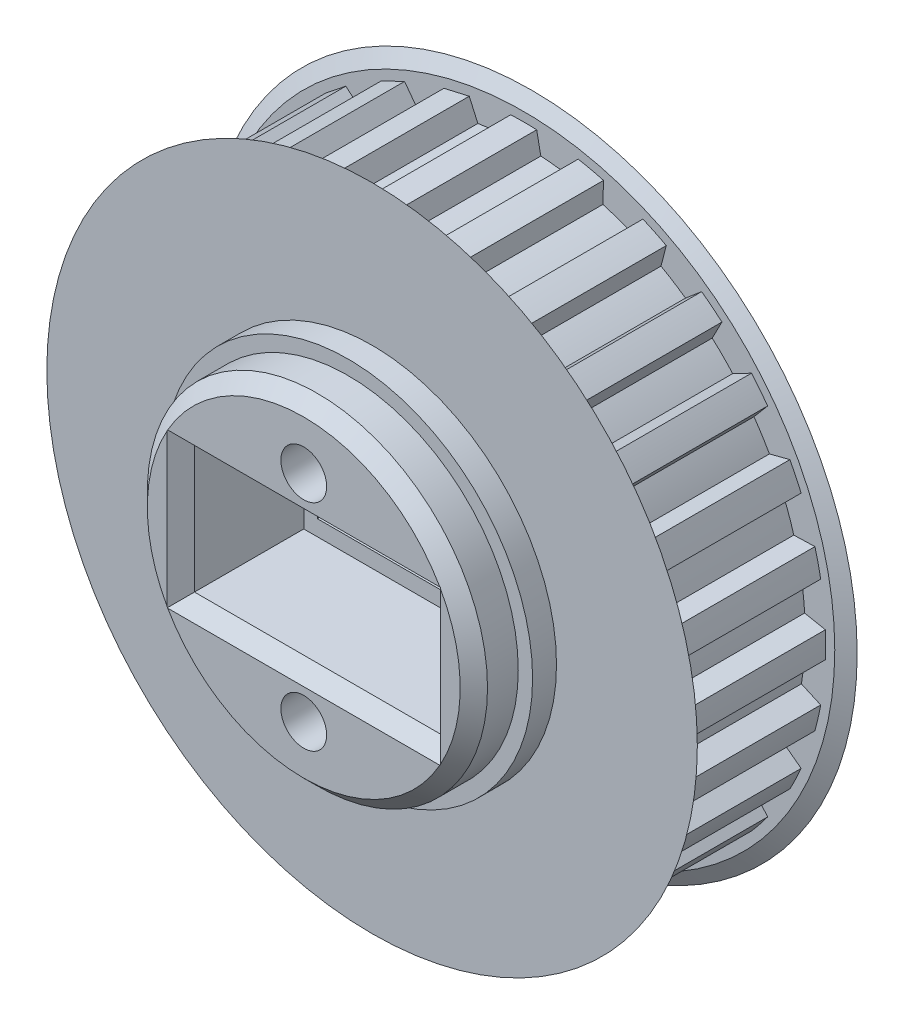
SolidWorks part; units mm, degrees
material "ABS"
ref_plane "Alzado" through (0, 0, 0) normal (0, 0, 1) x (1, 0, 0)
ref_plane "Planta" through (0, 0, 0) normal (0, 1, 0) x (1, 0, 0)
ref_plane "Vista lateral" through (0, 0, 0) normal (1, 0, 0) x (0, 0, -1)
sketch "Croquis1" plane through (0, 0, 0) normal (0, 0, 1) x (1, 0, 0)
  line L0 (0, 0) -> (0, 14.5885) construction
  line L1 (-0.95, 22.0796) -> (-1.25, 20.562)
  line L2 (0.95, 22.0796) -> (1.25, 20.562)
  line L3 (5.8393, 21.3146) -> (5.7941, 19.7684)
  line L4 (3.987, 21.7374) -> (3.3568, 20.3247)
  line L5 (10.4359, 19.4808) -> (10.0477, 17.9834)
  line L6 (8.724, 20.3052) -> (7.7953, 19.0681)
  line L7 (14.5091, 16.6702) -> (13.7975, 15.2967)
  line L8 (13.0236, 17.8548) -> (11.8429, 16.8554)
  line L9 (17.8548, 13.0236) -> (16.8554, 11.8429)
  line L10 (16.6702, 14.5091) -> (15.2967, 13.7975)
  line L11 (20.3052, 8.724) -> (19.0681, 7.7953)
  line L12 (19.4808, 10.4359) -> (17.9834, 10.0477)
  line L13 (21.7374, 3.987) -> (20.3247, 3.3568)
  line L14 (21.3146, 5.8393) -> (19.7684, 5.7941)
  line L15 (22.0796, -0.95) -> (20.562, -1.25)
  line L16 (22.0796, 0.95) -> (20.562, 1.25)
  line L17 (21.3146, -5.8393) -> (19.7684, -5.7941)
  line L18 (21.7374, -3.987) -> (20.3247, -3.3568)
  line L19 (19.4808, -10.4359) -> (17.9834, -10.0477)
  line L20 (20.3052, -8.724) -> (19.0681, -7.7953)
  line L21 (16.6702, -14.5091) -> (15.2967, -13.7975)
  line L22 (17.8548, -13.0236) -> (16.8554, -11.8429)
  line L23 (13.0236, -17.8548) -> (11.8429, -16.8554)
  line L24 (14.5091, -16.6702) -> (13.7975, -15.2967)
  line L25 (8.724, -20.3052) -> (7.7953, -19.0681)
  line L26 (10.4359, -19.4808) -> (10.0477, -17.9834)
  line L27 (3.987, -21.7374) -> (3.3568, -20.3247)
  line L28 (5.8393, -21.3146) -> (5.7941, -19.7684)
  line L29 (-0.95, -22.0796) -> (-1.25, -20.562)
  line L30 (0.95, -22.0796) -> (1.25, -20.562)
  line L31 (-5.8393, -21.3146) -> (-5.7941, -19.7684)
  line L32 (-3.987, -21.7374) -> (-3.3568, -20.3247)
  line L33 (-10.4359, -19.4808) -> (-10.0477, -17.9834)
  line L34 (-8.724, -20.3052) -> (-7.7953, -19.0681)
  line L35 (-14.5091, -16.6702) -> (-13.7975, -15.2967)
  line L36 (-13.0236, -17.8548) -> (-11.8429, -16.8554)
  line L37 (-17.8548, -13.0236) -> (-16.8554, -11.8429)
  line L38 (-16.6702, -14.5091) -> (-15.2967, -13.7975)
  line L39 (-20.3052, -8.724) -> (-19.0681, -7.7953)
  line L40 (-19.4808, -10.4359) -> (-17.9834, -10.0477)
  line L41 (-21.7374, -3.987) -> (-20.3247, -3.3568)
  line L42 (-21.3146, -5.8393) -> (-19.7684, -5.7941)
  line L43 (-22.0796, 0.95) -> (-20.562, 1.25)
  line L44 (-22.0796, -0.95) -> (-20.562, -1.25)
  line L45 (-21.3146, 5.8393) -> (-19.7684, 5.7941)
  line L46 (-21.7374, 3.987) -> (-20.3247, 3.3568)
  line L47 (-19.4808, 10.4359) -> (-17.9834, 10.0477)
  line L48 (-20.3052, 8.724) -> (-19.0681, 7.7953)
  line L49 (-16.6702, 14.5091) -> (-15.2967, 13.7975)
  line L50 (-17.8548, 13.0236) -> (-16.8554, 11.8429)
  line L51 (-13.0236, 17.8548) -> (-11.8429, 16.8554)
  line L52 (-14.5091, 16.6702) -> (-13.7975, 15.2967)
  line L53 (-14.5091, 16.6702) -> (-13.0236, 17.8548)
  line L54 (-8.724, 20.3052) -> (-7.7953, 19.0681)
  line L55 (-10.4359, 19.4808) -> (-10.0477, 17.9834)
  line L56 (-10.4359, 19.4808) -> (-8.724, 20.3052)
  line L57 (-3.987, 21.7374) -> (-3.3568, 20.3247)
  line L58 (-5.8393, 21.3146) -> (-5.7941, 19.7684)
  line L59 (-5.8393, 21.3146) -> (-3.987, 21.7374)
  arc A0 (-13.7975, 15.2967) -> (-15.2967, 13.7975) centre (0, 0) ccw
  arc A1 (3.3568, 20.3247) -> (1.25, 20.562) centre (0, 0) ccw
  arc A2 (-10.0477, 17.9834) -> (-11.8429, 16.8554) centre (0, 0) ccw
  arc A3 (-5.7941, 19.7684) -> (-7.7953, 19.0681) centre (0, 0) ccw
  arc A9 (-16.6702, 14.5091) -> (-17.8548, 13.0236) centre (0, 0) ccw
  arc A10 (-19.4808, 10.4359) -> (-20.3052, 8.724) centre (0, 0) ccw
  arc A11 (5.8393, 21.3146) -> (3.987, 21.7374) centre (0, 0) ccw
  arc A12 (0.95, 22.0796) -> (-0.95, 22.0796) centre (0, 0) ccw
  arc A16 (10.4359, 19.4808) -> (8.724, 20.3052) centre (0, 0) ccw
  arc A17 (14.5091, 16.6702) -> (13.0236, 17.8548) centre (0, 0) ccw
  arc A18 (17.8548, 13.0236) -> (16.6702, 14.5091) centre (0, 0) ccw
  arc A19 (20.3052, 8.724) -> (19.4808, 10.4359) centre (0, 0) ccw
  arc A20 (21.7374, 3.987) -> (21.3146, 5.8393) centre (0, 0) ccw
  arc A21 (22.0796, -0.95) -> (22.0796, 0.95) centre (0, 0) ccw
  arc A22 (21.3146, -5.8393) -> (21.7374, -3.987) centre (0, 0) ccw
  arc A23 (19.4808, -10.4359) -> (20.3052, -8.724) centre (0, 0) ccw
  arc A24 (16.6702, -14.5091) -> (17.8548, -13.0236) centre (0, 0) ccw
  arc A25 (13.0236, -17.8548) -> (14.5091, -16.6702) centre (0, 0) ccw
  arc A26 (-5.8393, -21.3146) -> (-3.987, -21.7374) centre (0, 0) ccw
  arc A27 (-10.4359, -19.4808) -> (-8.724, -20.3052) centre (0, 0) ccw
  arc A28 (-14.5091, -16.6702) -> (-13.0236, -17.8548) centre (0, 0) ccw
  arc A29 (-20.3052, -8.724) -> (-19.4808, -10.4359) centre (0, 0) ccw
  arc A30 (-21.7374, -3.987) -> (-21.3146, -5.8393) centre (0, 0) ccw
  arc A31 (-22.0796, 0.95) -> (-22.0796, -0.95) centre (0, 0) ccw
  arc A32 (-21.3146, 5.8393) -> (-21.7374, 3.987) centre (0, 0) ccw
  arc A33 (-0.95, -22.0796) -> (0.95, -22.0796) centre (0, 0) ccw
  arc A34 (3.987, -21.7374) -> (5.8393, -21.3146) centre (0, 0) ccw
  arc A35 (8.724, -20.3052) -> (10.4359, -19.4808) centre (0, 0) ccw
  arc A36 (7.7953, 19.0681) -> (5.7941, 19.7684) centre (0, 0) ccw
  arc A37 (11.8429, 16.8554) -> (10.0477, 17.9834) centre (0, 0) ccw
  arc A39 (-1.25, 20.562) -> (-3.3568, 20.3247) centre (0, 0) ccw
  arc A43 (15.2967, 13.7975) -> (13.7975, 15.2967) centre (0, 0) ccw
  arc A44 (17.9834, 10.0477) -> (16.8554, 11.8429) centre (0, 0) ccw
  arc A45 (19.7684, 5.7941) -> (19.0681, 7.7953) centre (0, 0) ccw
  arc A46 (20.562, 1.25) -> (20.3247, 3.3568) centre (0, 0) ccw
  arc A47 (20.3247, -3.3568) -> (20.562, -1.25) centre (0, 0) ccw
  arc A48 (19.0681, -7.7953) -> (19.7684, -5.7941) centre (0, 0) ccw
  arc A49 (16.8554, -11.8429) -> (17.9834, -10.0477) centre (0, 0) ccw
  arc A50 (13.7975, -15.2967) -> (15.2967, -13.7975) centre (0, 0) ccw
  arc A51 (10.0477, -17.9834) -> (11.8429, -16.8554) centre (0, 0) ccw
  arc A52 (5.7941, -19.7684) -> (7.7953, -19.0681) centre (0, 0) ccw
  arc A53 (1.25, -20.562) -> (3.3568, -20.3247) centre (0, 0) ccw
  arc A54 (-3.3568, -20.3247) -> (-1.25, -20.562) centre (0, 0) ccw
  arc A55 (-7.7953, -19.0681) -> (-5.7941, -19.7684) centre (0, 0) ccw
  arc A56 (-11.8429, -16.8554) -> (-10.0477, -17.9834) centre (0, 0) ccw
  arc A57 (-15.2967, -13.7975) -> (-13.7975, -15.2967) centre (0, 0) ccw
  arc A58 (-17.9834, -10.0477) -> (-16.8554, -11.8429) centre (0, 0) ccw
  arc A59 (-19.7684, -5.7941) -> (-19.0681, -7.7953) centre (0, 0) ccw
  arc A60 (-20.562, -1.25) -> (-20.3247, -3.3568) centre (0, 0) ccw
  arc A61 (-20.3247, 3.3568) -> (-20.562, 1.25) centre (0, 0) ccw
  arc A62 (-19.0681, 7.7953) -> (-19.7684, 5.7941) centre (0, 0) ccw
  arc A63 (-16.8554, 11.8429) -> (-17.9834, 10.0477) centre (0, 0) ccw
  arc A71 (-17.8548, -13.0236) -> (-16.6702, -14.5091) centre (0, 0) ccw
  circle A72 centre (0, 0) radius 1.5
  point P151 (0, 0)
  dimension "D1" = 22.1
  dimension "D6" = 3
  dimension "D5" = 1.5
  dimension "D2" = 2.5
  dimension "D3" = 1.9
  dimension "D4" = 28
extrude "Saliente-Extruir1" add sketch "Croquis1" along normal blind 10.5
sketch "Croquis2" plane through (0, 0, 10.5) normal (0, 0, 1) x (1, 0, 0)
  circle A0 centre (0, 0) radius 24.5
  circle A1 centre (0, 0) radius 1.5
  circle A2 centre (0, 0) radius 1.5 construction
  dimension "D1" = 49
extrude "Saliente-Extruir2" add sketch "Croquis2" along normal blind 0.6
sketch "Croquis3" plane through (0, 0, 11.1) normal (0, 0, 1) x (1, 0, 0)
  circle A0 centre (0, 0) radius 1.5
  circle A1 centre (0, 0) radius 12.45
  circle A3 centre (0, 0) radius 1.5 construction
  dimension "D1" = 24.9
sketch "Croquis4" plane through (0, 0, 0) normal (0, 0, -1) x (-1, 0, 0)
  circle A0 centre (0, 0) radius 1.5
  circle A1 centre (0, 0) radius 12.45
  circle A2 centre (0, 0) radius 1.5 construction
  dimension "D1" = 24.9
extrude "Saliente-Extruir4" add sketch "Croquis4" along normal blind 4.25
sketch "Croquis6" plane through (0, 0, 0) normal (0, 0, -1) x (-1, 0, 0)
  circle A0 centre (0, 0) radius 24.5
  circle A1 centre (0, 0) radius 1.5
  circle A2 centre (0, 0) radius 1.5 construction
  dimension "D1" = 49
extrude "Saliente-Extruir6" add sketch "Croquis6" along normal blind 0.6
sketch "Croquis5" plane through (0, 0, -0.6) normal (0, 0, -1) x (-1, 0, 0)
  circle A0 centre (0, 0) radius 1.5
  circle A1 centre (0, 0) radius 13.5
  circle A2 centre (0, 0) radius 1.5 construction
  dimension "D1" = 27
extrude "Saliente-Extruir5" add sketch "Croquis5" along normal blind 1.75
chamfer "Chaflán2" distance 1 angle 60 2 edges at (-24.5, 0, 0) (24.5, 0, 10.5)
extrude "Saliente-Extruir7" add sketch "Croquis3" along normal blind 5
chamfer "Chaflán4" distance 1 angle 45 1 edges at (12.45, 0, 16.1)
sketch "Croquis7" plane through (0, 0, 11.1) normal (0, 0, 1) x (1, 0, 0)
  circle A0 centre (0, 0) radius 1.5
  circle A1 centre (0, 0) radius 13.5
  circle A2 centre (0, 0) radius 1.5 construction
  dimension "D1" = 27
extrude "Saliente-Extruir8" add sketch "Croquis7" along normal blind 1.75
sketch "Croquis8" plane through (0, 0, 0) normal (0, 0, 1) x (1, 0, 0)
  line L0 (0, 0) -> (6.706, 0) construction
  line L1 (-8, 3.5) -> (8, 3.5)
  line L2 (-8, 3.5) -> (-8, -3.5)
  line L3 (-8, -3.5) -> (8, -3.5)
  line L4 (8, 3.5) -> (8, -3.5)
  line L5 (-8, 3.5) -> (8, -3.5) construction
  line L6 (-8, -3.5) -> (8, 3.5) construction
  circle A0 centre (0, 7.8756) radius 1.675
  circle A1 centre (0, -7.8756) radius 1.675
  point P0 (0, 0)
  dimension "D1" = 3.35
  dimension "D2" = 7
  dimension "D3" = 16
extrude "Cortar-Extruir1" cut sketch "Croquis8" against normal through all both and the other way through all
sketch "Croquis10" plane through (0, 0, 16.1) normal (0, 0, 1) x (1, 0, 0)
  line L1 (9, 4.65) -> (-9, 4.65)
  line L2 (9, 4.65) -> (9, -4.65)
  line L3 (9, -4.65) -> (-9, -4.65)
  line L4 (-9, 4.65) -> (-9, -4.65)
  line L5 (9, 4.65) -> (-9, -4.65) construction
  line L6 (9, -4.65) -> (-9, 4.65) construction
  point P0 (0, 0)
  dimension "D1" = 9.3
  dimension "D2" = 18
extrude "Cortar-Extruir3" cut sketch "Croquis10" against normal blind 9
chamfer "Chaflán5" distance 1 angle 45 8 edges at (-8, 0, -4.25) (0, 3.5, -4.25) (8, 0, -4.25) (0, -3.5, -4.25) (9, 0, 16.1) (0, 4.65, 16.1) (-9, 0, 16.1) (0, -4.65, 16.1)
sketch "Sketch1" plane through (0, 0, -4.25) normal (0, 0, -1) x (-1, 0, 0)
  circle A0 centre (0, 0) radius 12.45
  circle A1 centre (0, 0) radius 12.45 construction
  circle A2 centre (0, 7.8756) radius 1.675
  circle A3 centre (0, -7.8756) radius 1.675
  circle A4 centre (0, 7.8756) radius 1.675 construction
extrude "Boss-Extrude1" add sketch "Sketch1" against normal blind 5
sketch "Sketch2" plane through (0, 0, -4.25) normal (0, 0, -1) x (-1, 0, 0)
  line L0 (0, 17.274) -> (0, -20.0751) construction
  line L1 (-7.5, 0) -> (7.5, 0) construction
  circle A0 centre (-7.5, 0) radius 1.45
  circle A1 centre (7.5, 0) radius 1.45
  dimension "D1" = 2.9
  dimension "D2" = 15
extrude "Cut-Extrude1" cut sketch "Sketch2" against normal through all
sketch "Sketch4" plane through (0, 0, 16.1) normal (0, 0, 1) x (1, 0, 0)
  line L0 (-8, -3.5) -> (8, -3.5) construction
  line L1 (4, 3.5) -> (-4, 3.5)
  line L2 (4, 3.5) -> (4, -3.5)
  line L3 (4, -3.5) -> (-4, -3.5)
  line L4 (-4, 3.5) -> (-4, -3.5)
  line L5 (4, 3.5) -> (-4, -3.5) construction
  line L6 (4, -3.5) -> (-4, 3.5) construction
  point P0 (0, 0)
  dimension "D1" = 8
extrude "Cut-Extrude2" cut sketch "Sketch4" against normal blind 21
chamfer "Chamfer3" distance 1 angle 45 4 edges at (-4, 0, -4.25) (0, 3.5, -4.25) (4, 0, -4.25) (0, -3.5, -4.25)
chamfer "Chamfer2" distance 0.75 angle 45 1 edges at (-12.45, 0, -4.25)
